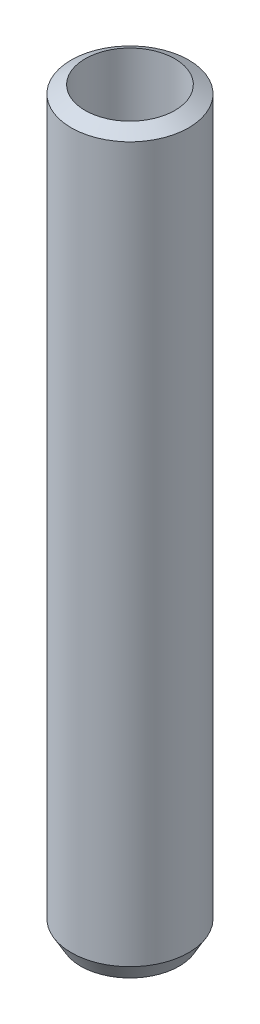
SolidWorks part; units mm, degrees
ref_plane "Front Plane" through (0, 0, 0) normal (0, 0, 1) x (1, 0, 0)
ref_plane "Top Plane" through (0, 0, 0) normal (0, 1, 0) x (1, 0, 0)
ref_plane "Right Plane" through (0, 0, 0) normal (1, 0, 0) x (0, 0, -1)
sketch "Sketch1" plane through (0, 0, 0) normal (0, 1, 0) x (1, 0, 0)
  circle A0 centre (0, 0) radius 25
  dimension "SHAFT_OD" = 50
extrude "Boss-Extrude1" add sketch "Sketch1" along normal blind 315.095
sketch "Sketch2" plane through (0, 0, 0) normal (0, 1, 0) x (1, 0, 0)
  circle A0 centre (0, 0) radius 19.0793
  dimension "BORE_D" = 38.1585
extrude "Cut-Extrude1" cut sketch "Sketch2" along normal through all
chamfer "Chamfer1" distance 4.0666 angle 60 2 edges at (0, 315.095, 25) (0, 0, 25) first distance on face at (0, 315.095, 25) first distance on face at (0, 0, 19.0793)
